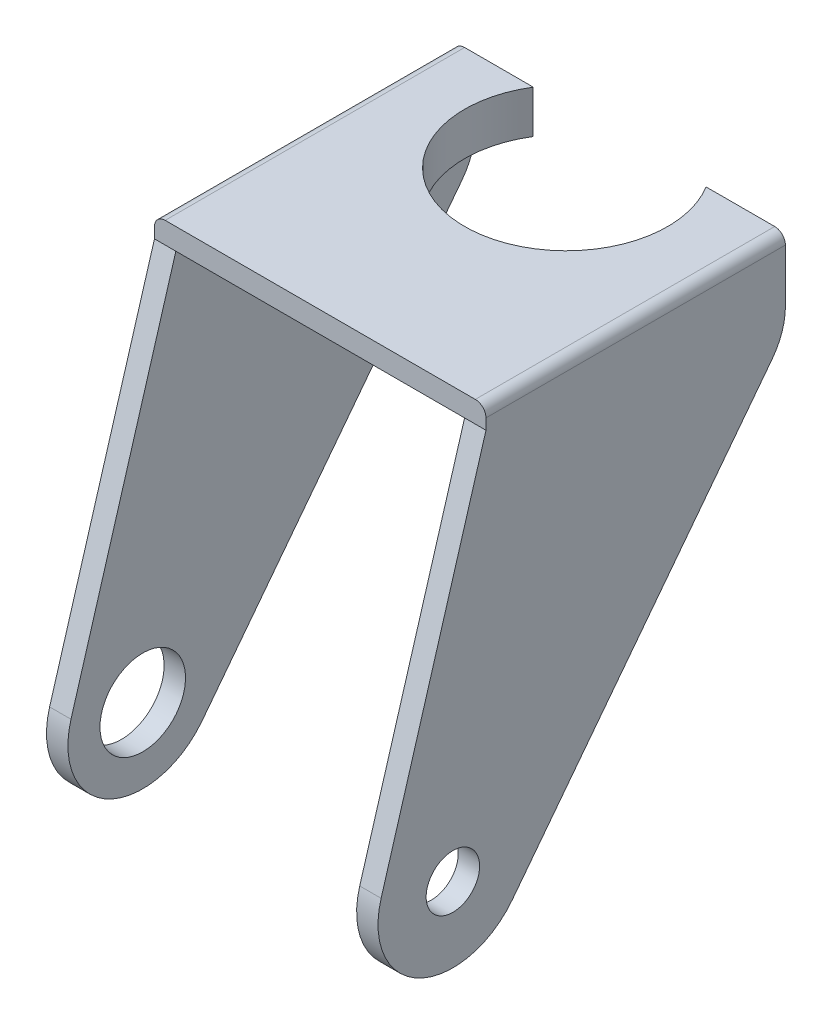
SolidWorks part; units mm, degrees
ref_plane "Front Plane" through (0, 0, 0) normal (0, 0, 1) x (1, 0, 0)
ref_plane "Top Plane" through (0, 0, 0) normal (0, 1, 0) x (1, 0, 0)
ref_plane "Right Plane" through (0, 0, 0) normal (1, 0, 0) x (0, 0, -1)
sketch "Sketch1" plane through (0, 0, 0) normal (1, 0, 0) x (0, 0, -1)
  line L0 (-6.71, 1.994) -> (3.0966, 34.994)
  line L1 (3.0966, 34.994) -> (3.0966, 36.994)
  line L2 (3.0966, 36.994) -> (31.0966, 36.994)
  line L3 (31.0966, 36.994) -> (31.0966, 31.0323)
  line L4 (29.8549, 27.3775) -> (5.5514, -4.264)
  arc A0 (-6.71, 1.994) -> (5.5514, -4.264) centre (0, 0) ccw
  arc A1 (31.0966, 31.0323) -> (29.8549, 27.3775) centre (25.0966, 31.0323) cw
  point P11 (31.0966, 28.994)
  dimension "D1" = 14
  dimension "D6" = 6
  dimension "D2" = 35
  dimension "D3" = 2
  dimension "D4" = 28
  dimension "D5" = 8
extrude "Boss-Extrude1" add sketch "Sketch1" against normal blind 2
ref_plane "Plane1" through (-15.5, 0, 0) normal (1, 0, 0) x (0, 0, -1)
mirror "Mirror1" about plane through (-15.5, 0, 0) normal (1, 0, 0) of bodies 101
sketch "Sketch2" plane through (0, 36.994, 0) normal (0, 1, 0) x (1, 0, 0)
  line L1 (-31, 31.0966) -> (0, 31.0966)
  line L2 (-31, 31.0966) -> (-31, 3.0966)
  line L3 (-31, 3.0966) -> (0, 3.0966)
  line L4 (0, 31.0966) -> (0, 3.0966)
extrude "Boss-Extrude2" add sketch "Sketch2" against normal blind 2
sketch "Sketch3" plane through (0, 36.994, 0) normal (0, 1, 0) x (1, 0, 0)
  line L0 (0, 17.0966) -> (-31, 17.0966) construction
  line L1 (0, 31.0966) -> (0, 3.0966) construction
  line L2 (-31, 31.0966) -> (-31, 3.0966) construction
  line L3 (-31, 17.0966) -> (-15.5, 3.0966) construction
  line L4 (-31, 3.0966) -> (0, 3.0966) construction
  line L5 (-15.5, 3.0966) -> (-15.5, 31.0966) construction
  line L6 (-31, 31.0966) -> (0, 31.0966) construction
  line L10 (-7.4196, 31.0923) -> (-5.1438, 31.0966)
  line L11 (-23.5804, 31.0923) -> (-25.8562, 31.0966)
  arc A0 (-23.5804, 31.0923) -> (-7.4196, 31.0923) centre (-15.5, 26.0966) ccw
  arc A1 (-25.8562, 31.0966) -> (-5.1438, 31.0966) centre (-15.5, 26.0966) ccw
  arc A2 (-25.2816, 32.144) -> (-5.7184, 32.144) centre (-15.5, 26.0966) ccw construction
  dimension "D3" = 19
  dimension "D5" = 2
extrude "Boss-Extrude3" add sketch "Sketch3" against normal blind 4
sketch "Sketch4" plane through (0, 34.994, 0) normal (0, -1, 0) x (1, 0, 0)
  line L3 (-5.1438, -31.0966) -> (-7.4196, -31.0923)
  line L4 (-23.5804, -31.0923) -> (-25.8562, -31.0966)
  line L5 (-25.8562, -31.0966) -> (-5.1438, -31.0966)
  line L6 (-5.1438, -31.0966) -> (-7.4196, -31.0923)
  line L7 (-23.5804, -31.0923) -> (-25.8562, -31.0966)
  line L8 (-25.8562, -31.0966) -> (-5.1438, -31.0966)
  arc A1 (-7.4196, -31.0923) -> (-23.5804, -31.0923) centre (-15.5, -26.0966) ccw
  arc A2 (-7.4196, -31.0923) -> (-23.5804, -31.0923) centre (-15.5, -26.0966) ccw
  dimension "D1" = 0
extrude "Cut-Extrude1" cut sketch "Sketch4" against normal blind 4
fillet "Fillet1" radius 1 2 edges at (-31, 36.994, -17.0966) (0, 36.994, -17.0966)
sketch "Sketch5" plane through (0, 0, 0) normal (1, 0, 0) x (0, 0, -1)
  circle A0 centre (0, 0) radius 4
  dimension "D1" = 8
extrude "Cut-Extrude2" cut sketch "Sketch5" against normal blind 10 from surface starting at face at (-29, 20.1542, -15.2809)
sketch "Sketch6" plane through (0, 0, 0) normal (1, 0, 0) x (0, 0, -1)
  circle A2 centre (0, 0) radius 2.5
  dimension "D1" = 5
extrude "Cut-Extrude3" cut sketch "Sketch6" against normal blind 10
